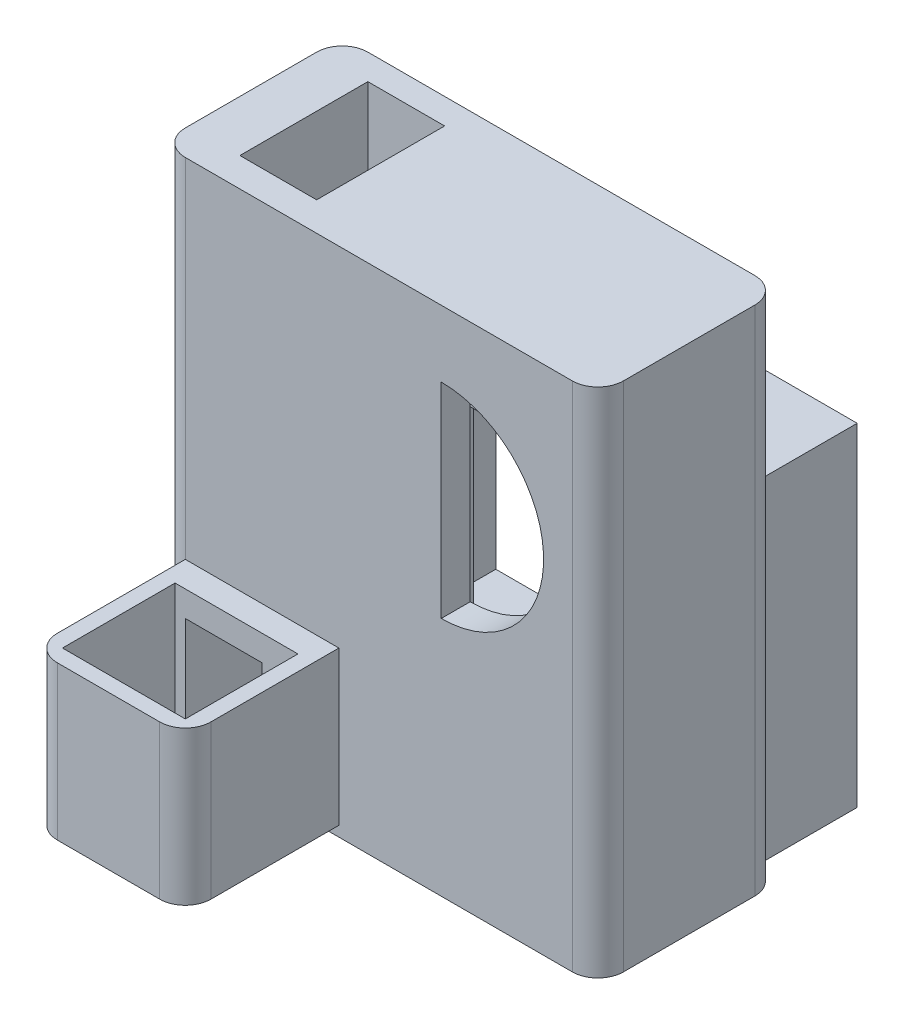
SolidWorks part; units mm, degrees
ref_plane "Alzado" through (0, 0, 0) normal (0, 0, 1) x (1, 0, 0)
ref_plane "Planta" through (0, 0, 0) normal (0, 1, 0) x (1, 0, 0)
ref_plane "Vista lateral" through (0, 0, 0) normal (1, 0, 0) x (0, 0, -1)
sketch "Croquis1" plane through (0, 0, 0) normal (0, 1, 0) x (1, 0, 0)
  line L1 (-42.8, 17.83) -> (42.8, 17.83)
  line L2 (-42.8, 17.83) -> (-42.8, -17.83)
  line L3 (-42.8, -17.83) -> (42.8, -17.83)
  line L4 (42.8, 17.83) -> (42.8, -17.83)
  line L5 (-42.8, 17.83) -> (42.8, -17.83) construction
  line L6 (-42.8, -17.83) -> (42.8, 17.83) construction
  point P0 (0, 0)
  dimension "D1" = 85.6
  dimension "D2" = 35.66
extrude "Saliente-Extruir1" add sketch "Croquis1" along normal blind 100
sketch "Croquis2" plane through (0, 100, 0) normal (0, 1, 0) x (1, 0, 0)
  line L0 (42.8, 17.83) -> (-42.8, 17.83) construction
  line L1 (-32.8, 12.83) -> (-17.8, 12.83)
  line L2 (-32.8, 12.83) -> (-32.8, -12.17)
  line L3 (-32.8, -12.17) -> (-17.8, -12.17)
  line L4 (-17.8, 12.83) -> (-17.8, -12.17)
  line L5 (-32.8, 12.83) -> (-17.8, -12.17) construction
  line L6 (-32.8, -12.17) -> (-17.8, 12.83) construction
  line L7 (-42.8, 17.83) -> (-42.8, -17.83) construction
  point P0 (-25.3, 0.33)
  dimension "D1" = 5
  dimension "D2" = 10
  dimension "D3" = 15
  dimension "D4" = 25
extrude "Cortar-Extruir1" cut sketch "Croquis2" against normal blind 92
sketch "Croquis3" plane through (0, 0, 17.83) normal (0, 0, 1) x (1, 0, 0)
  line L0 (-42.8, 100) -> (-42.8, 0) construction
  line L1 (-37.8, 32) -> (-7.8, 32)
  line L2 (-37.8, 32) -> (-37.8, 2)
  line L3 (-37.8, 2) -> (-7.8, 2)
  line L4 (-7.8, 32) -> (-7.8, 2)
  line L5 (-37.8, 32) -> (-7.8, 2) construction
  line L6 (-37.8, 2) -> (-7.8, 32) construction
  line L9 (-42.8, 0) -> (42.8, 0) construction
  point P0 (-22.8, 17)
  dimension "D1" = 5
  dimension "D2" = 2
  dimension "D3" = 30
  dimension "D4" = 30
extrude "Saliente-Extruir2" add sketch "Croquis3" along normal blind 30
sketch "Croquis4" plane through (0, 2, 0) normal (0, -1, 0) x (1, 0, 0)
  line L0 (-7.8, 47.83) -> (-7.8, 17.83) construction
  line L1 (-37.8, 47.83) -> (-37.8, 17.83) construction
  line L2 (-37.8, 47.83) -> (-7.8, 47.83) construction
  line L20 (-34.8, 22.83) -> (-10.8, 22.83)
  line L21 (-10.8, 22.83) -> (-10.8, 44.83)
  line L22 (-10.8, 44.83) -> (-34.8, 44.83)
  line L23 (-34.8, 44.83) -> (-34.8, 22.83)
  dimension "D1" = 3
  dimension "D2" = 3
  dimension "D3" = 3
extrude "Cortar-Extruir2" cut sketch "Croquis4" against normal up to surface (30 mm away) up to face at (-22.8, 32, 32.83)
sketch "Croquis6" plane through (0, 0, 17.83) normal (0, 0, 1) x (1, 0, 0)
  line L12 (-17.8, 7) -> (-17.8, 27)
  line L13 (-17.8, 27) -> (-32.8, 27)
  line L14 (-32.8, 27) -> (-32.8, 7)
  line L15 (-32.8, 7) -> (-17.8, 7)
  dimension "D1" = 15
fillet "Redondeo1" radius 5 6 edges at (42.8, 50, 17.83) (42.8, 50, -17.83) (-42.8, 50, -17.83) (-42.8, 50, 17.83) (-7.8, 17, 47.83) (-37.8, 17, 47.83)
sketch "Croquis8" plane through (0, 0, -17.83) normal (0, 0, -1) x (-1, 0, 0)
  line L0 (37.8, 0) -> (37.8, 100) construction
  line L1 (-37.8, 0) -> (37.8, 0)
  line L2 (-37.8, 0) -> (-37.8, 65)
  line L3 (-37.8, 65) -> (37.8, 65)
  line L4 (37.8, 0) -> (37.8, 65)
  dimension "D1" = 75.6
  dimension "D2" = 65
extrude "Saliente-Extruir3" add sketch "Croquis8" along normal blind 20
extrude "Cortar-Extruir3" cut sketch "Croquis6" against normal blind 10 and the other way blind 10
sketch "Croquis9" plane through (0, 2, 0) normal (0, -1, 0) x (1, 0, 0)
  line L0 (-10.8, 22.83) -> (-10.8, 44.83) construction
  line L1 (-34.8, 22.83) -> (-10.8, 22.83)
  line L2 (-34.8, 22.83) -> (-34.8, 44.83)
  line L3 (-34.8, 44.83) -> (-10.8, 44.83)
  line L4 (-10.8, 22.83) -> (-10.8, 44.83)
  line L5 (-10.8, 44.83) -> (-34.8, 44.83) construction
extrude "Saliente-Extruir4" add sketch "Croquis9" along normal blind 2 draft 60 separate body
sketch "Croquis10" plane through (0, 0, 0) normal (0, -1, 0) x (1, 0, 0)
  line L1 (-31.3359, 26.2941) -> (-14.2641, 26.2941)
  line L2 (-31.3359, 26.2941) -> (-31.3359, 41.3659)
  line L3 (-31.3359, 41.3659) -> (-14.2641, 41.3659)
  line L4 (-14.2641, 26.2941) -> (-14.2641, 41.3659)
extrude "Cortar-Extruir4" cut sketch "Croquis10" against normal up to surface (2 mm away) draft 25
sketch "Croquis12" plane through (0, 0, -37.83) normal (0, 0, -1) x (-1, 0, 0)
  line L8 (-32.8, 60) -> (-32.8, 5)
  line L9 (-32.8, 5) -> (32.8, 5)
  line L10 (32.8, 5) -> (32.8, 60)
  line L11 (32.8, 60) -> (-32.8, 60)
  line L12 (-32.8, 60) -> (-32.8, 5)
  line L13 (-32.8, 5) -> (32.8, 5)
  line L14 (32.8, 5) -> (32.8, 60)
  line L15 (32.8, 60) -> (-32.8, 60)
  dimension "D1" = 5
extrude "Cortar-Extruir6" cut sketch "Croquis12" against normal up to surface (20 mm away) up to face at (0, 82.5, -17.83)
sketch "Croquis17" plane through (0, 0, -17.83) normal (0, 0, -1) x (-1, 0, 0)
  line L0 (-32.8, 5) -> (32.8, 5) construction
  line L1 (-32.8, 60) -> (-2.8, 60)
  line L2 (-32.8, 60) -> (-32.8, 5)
  line L3 (-32.8, 5) -> (-2.8, 5)
  line L4 (-2.8, 60) -> (-2.8, 5)
  dimension "D1" = 30
extrude "Cortar-Extruir11" cut sketch "Croquis17" against normal blind 30
sketch "Croquis19" plane through (0, 0, 12.17) normal (0, 0, -1) x (-1, 0, 0)
  line L0 (-2.8, 45) -> (-2.8, 85)
  line L1 (-2.8, 5) -> (-2.8, 60) construction
  line L2 (-37.8, 100) -> (37.8, 100) construction
  line L3 (-2.8, 85) -> (-32.8, 85)
  line L4 (-32.8, 85) -> (-32.8, 60)
  line L5 (-32.8, 60) -> (-32.8, 5) construction
  line L6 (32.8, 60) -> (-32.8, 60) construction
  line L7 (-32.8, 60) -> (-22.1649, 60)
  line L8 (-2.8, 60) -> (-32.8, 60) construction
  arc A0 (-2.8, 85) -> (-2.8, 45) centre (-2.8, 65) ccw
  line M4 (-2.8, 60) -> (-32.8, 60)
  dimension "D2" = 20
  dimension "D1" = 15
extrude "Cortar-Extruir18" cut sketch "Croquis19" along normal blind 20 contours A0 L3 L4 M4 | L0 A0 M4
sketch "Croquis20" plane through (0, 0, 17.83) normal (0, 0, 1) x (1, 0, 0)
  line L0 (12.2, 47) -> (12.2, 87)
  line L1 (-37.8, 100) -> (37.8, 100) construction
  line L2 (37.8, 0) -> (37.8, 100) construction
  arc A0 (12.2, 87) -> (12.2, 47) centre (12.2, 67) cw
  dimension "D1" = 40
  dimension "D2" = 13
  dimension "D3" = 25.6
extrude "Cortar-Extruir19" cut sketch "Croquis20" against normal up to surface (5.66 mm away) contours A0 L0 up to face at (17.8, 45, 12.17)
sketch "Croquis21" plane through (2.8, 0, 0) normal (1, 0, 0) x (0, 0, -1)
  line L6 (17.83, 5) -> (17.83, 60)
  line L7 (17.83, 60) -> (7.83, 60)
  line L8 (7.83, 60) -> (7.83, 85)
  line L9 (7.83, 85) -> (-12.17, 85)
  line L10 (-12.17, 85) -> (-12.17, 5)
  line L11 (-12.17, 5) -> (17.83, 5)
  line L12 (17.83, 5) -> (17.83, 60)
  line L13 (17.83, 60) -> (7.83, 60)
  line L14 (7.83, 60) -> (7.83, 85)
  line L15 (7.83, 85) -> (-12.17, 85)
  line L16 (-12.17, 85) -> (-12.17, 5)
  line L17 (-12.17, 5) -> (17.83, 5)
  dimension "D1" = 0
extrude "Cortar-Extruir20" cut sketch "Croquis21" against normal blind 20
sketch "Croquis22" plane through (0, 0, 12.17) normal (0, 0, -1) x (-1, 0, 0)
  line L6 (-12.2, 85) -> (-12.2, 47)
  line L7 (-20.9178, 85) -> (-32.8, 85)
  line L8 (-32.8, 85) -> (-32.8, 5)
  line L9 (-32.8, 5) -> (17.2, 5)
  line L10 (17.2, 5) -> (17.2, 85)
  line L11 (17.2, 85) -> (-12.2, 85)
  line L12 (-12.2, 85) -> (-12.2, 47)
  line L13 (-20.9178, 85) -> (-32.8, 85)
  line L14 (-32.8, 85) -> (-32.8, 5)
  line L15 (-32.8, 5) -> (17.2, 5)
  line L16 (17.2, 5) -> (17.2, 85)
  line L17 (17.2, 85) -> (-12.2, 85)
  arc A1 (-20.9178, 85) -> (-12.2, 47) centre (-12.2, 67) ccw
  arc A2 (-20.9178, 85) -> (-12.2, 47) centre (-12.2, 67) ccw
  dimension "D2" = 29.4
  dimension "D1" = 0
